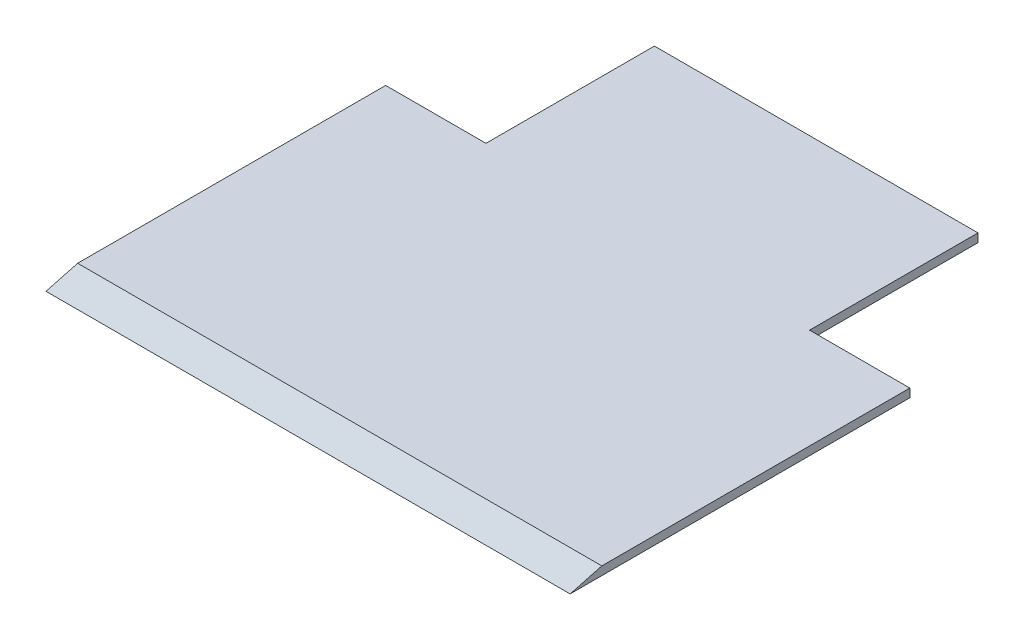
SolidWorks part; units mm, degrees
ref_plane "Alzado" through (0, 0, 0) normal (0, 0, 1) x (1, 0, 0)
ref_plane "Planta" through (0, 0, 0) normal (0, 1, 0) x (1, 0, 0)
ref_plane "Vista lateral" through (0, 0, 0) normal (1, 0, 0) x (0, 0, -1)
sketch "Croquis1" plane through (0, 0, 0) normal (1, 0, 0) x (0, 0, -1)
  line L0 (0, 0) -> (190, 0)
  line L1 (190, 0) -> (190, 3.17)
  line L2 (190, 3.17) -> (11.8306, 3.17)
  line L3 (0, 0) -> (11.8306, 3.17)
  dimension "D1" = 190
  dimension "D2" = 3.17
  dimension "D3" = 165
extrude "Saliente-Extruir1" add sketch "Croquis1" along normal blind 196
sketch "Croquis2" plane through (0, 0, 0) normal (0, -1, 0) x (-1, 0, 0)
  line L0 (0, 190) -> (0, 11.8306) construction
  line L1 (0, 127.0101) -> (-37.5, 127.0101)
  line L2 (0, 127.0101) -> (0, 190)
  line L3 (0, 190) -> (-37.5, 190)
  line L4 (-37.5, 127.0101) -> (-37.5, 190)
  line L5 (0, 127.0101) -> (-37.5, 190) construction
  line L6 (0, 190) -> (-37.5, 127.0101) construction
  line L7 (-196, 127.0101) -> (0, 127.0101) construction
  line L8 (-196, 190) -> (0, 190) construction
  line L9 (-37.5, 131.5) -> (-37.5, 190) construction
  point P4 (-18.75, 158.5051)
extrude "Cortar-Extruir1" cut sketch "Croquis2" against normal up to next
ref_plane "Plano1" through (98, 0, 0) normal (-1, 0, 0) x (0, 0, 1)
mirror "Simetría1" about plane through (98, 0, 0) normal (-1, 0, 0) of "Cortar-Extruir1"
